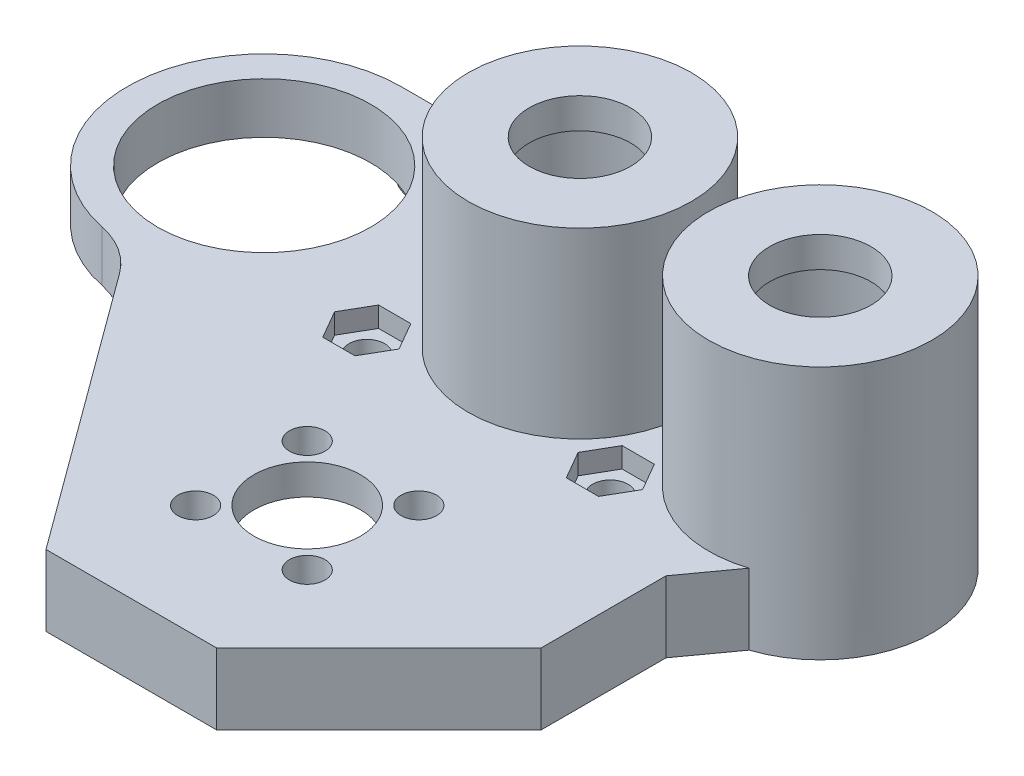
SolidWorks part; units mm, degrees
ref_plane "Front Plane" through (0, 0, 0) normal (0, 0, 1) x (1, 0, 0)
ref_plane "Top Plane" through (0, 0, 0) normal (0, 1, 0) x (1, 0, 0)
ref_plane "Right Plane" through (0, 0, 0) normal (1, 0, 0) x (0, 0, -1)
sketch "Sketch3" plane through (0, 0, 0) normal (0, 1, 0) x (1, 0, 0)
  line L1 (-31.113, 13.5) -> (23.69, 13.5)
  line L2 (-31.113, 13.5) -> (-31.113, -13.5)
  line L3 (-31.113, -13.5) -> (23.69, -13.5)
  line L4 (23.69, 13.5) -> (23.69, -13.5)
  line L5 (23.69, -13.5) -> (-31.113, -13.5)
  line L6 (23.69, -13.5) -> (23.69, -43.5)
  line L7 (23.69, -43.5) -> (-31.113, -43.5)
  line L8 (-31.113, -13.5) -> (-31.113, -43.5)
  circle A0 centre (-31.113, 0) radius 10.5
  circle A1 centre (-31.113, 0) radius 13.5
  circle A2 centre (0, -26.87) radius 5.25
  circle A3 centre (0, 0) radius 8
  circle A4 centre (23.69, 0) radius 8
  circle A5 centre (23.69, 0) radius 11
  dimension "D1" = 27
  dimension "D2" = 21
  dimension "D5" = 10.5
  dimension "D6" = 16
  dimension "D7" = 16
  dimension "D9" = 22
  dimension "D3" = 31.113
  dimension "D4" = 23.69
  dimension "D8" = 23.69
  dimension "D10" = 30
  dimension "D11" = 27
  dimension "D12" = 26.87
extrude "Boss-Extrude1" add sketch "Sketch3" along normal blind 7 contours L2 A1 A0 | A5 L4 L1 A1 L3 A3 | L2 A1 A0 | L4 A5 A4 | L3 L8 L7 L6 A2 | L4 A5 A4 region at (-21.7805, 0, -9.3325) region at (-3.7115, 0, -12.8891) region at (-31.4149, 0, -12) region at (-3.7115, 0, 14.1248) region at (31.2942, 0, -7.6042) region at (23.444, 0, -9.5)
sketch "Sketch4" plane through (0, 0, 0) normal (0, 1, 0) x (1, 0, 0)
  circle A0 centre (5.5, -21.37) radius 1.75
  circle A1 centre (0, -26.87) radius 5.25 construction
  circle A2 centre (5.5, -32.37) radius 1.75
  circle A3 centre (-5.5, -32.37) radius 1.75
  circle A4 centre (-5.5, -21.37) radius 1.75
  dimension "D3" = 3.5
  dimension "D4" = 3.5
  dimension "D7" = 3.5
  dimension "D9" = 3.5
  dimension "D1" = 5.5
  dimension "D2" = 5.5
  dimension "D5" = 5.5
  dimension "D6" = 5.5
  dimension "D8" = 11
  dimension "D10" = 11
  dimension "D11" = 11
  dimension "D12" = 11
extrude "Cut-Extrude3" cut sketch "Sketch4" along normal through all both and the other way through all
sketch "Sketch6" plane through (0, 7, 0) normal (0, 1, 0) x (1, 0, 0)
  circle A0 centre (23.69, 0) radius 8 construction
  circle A1 centre (0, 0) radius 8 construction
  circle A2 centre (23.69, 0) radius 8
  circle A3 centre (0, 0) radius 8
  circle A4 centre (23.69, 0) radius 11
  circle A5 centre (0, 0) radius 11
  dimension "D1" = 22
extrude "Boss-Extrude2" add sketch "Sketch6" along normal blind 15
sketch "Sketch7" plane through (0, 22, 0) normal (0, 1, 0) x (1, 0, 0)
  circle A0 centre (23.69, 0) radius 11 construction
  circle A1 centre (0, 0) radius 11 construction
  circle A2 centre (23.69, 0) radius 11
  circle A3 centre (0, 0) radius 11
  circle A4 centre (0, 0) radius 5
  circle A5 centre (23.69, 0) radius 5
  dimension "D1" = 10
  dimension "D2" = 10
extrude "Boss-Extrude3" add sketch "Sketch7" along normal blind 3
chamfer "Chamfer1" distance 2.5 angle 45 1 edges at (23.69, 3.5, -11)
sketch "Sketch8" plane through (0, 0, 0) normal (0, 1, 0) x (1, 0, 0)
  line L0 (-31.113, 0) -> (-31.113, 12.25)
  line L1 (-31.113, -13.5) -> (-51.113, -13.5)
  line L2 (-31.113, -13.5) -> (-31.113, 13.5)
  line L3 (-31.113, 13.5) -> (-51.113, 13.5)
  line L4 (-51.113, -13.5) -> (-51.113, 13.5)
  line L5 (-31.113, 12.25) -> (-13.613, 6.5)
  line L6 (-13.613, 6.5) -> (-13.613, -6.5)
  line L7 (-13.613, -6.5) -> (-31.113, -12.25)
  line L8 (-31.113, -12.25) -> (-31.113, 0)
  dimension "D1" = 20
  dimension "D2" = 12.25
  dimension "D3" = 12.25
  dimension "D4" = 27
  dimension "D5" = 17.5
  dimension "D6" = 6.5
  dimension "D7" = 6.5
extrude "Cut-Extrude4" cut sketch "Sketch8" along normal blind 2 contours L4 L1 L2 L0 L3 | L7 L6 L5 L0 L2 region at (-41.113, 0, 0) region at (-23.2574, 0, 0)
sketch "Sketch9" plane through (0, 0, 0) normal (0, 1, 0) x (1, 0, 0)
  circle A0 centre (12, 9) radius 1.75
  circle A1 centre (12, -9) radius 1.75
  circle A2 centre (-12, -9) radius 1.75
  circle A3 centre (-12, 9) radius 1.75
  dimension "D3" = 3.5
  dimension "D4" = 3.5
  dimension "D6" = 3.5
  dimension "D8" = 12
  dimension "D9" = 3.5
  dimension "D1" = 12
  dimension "D2" = 9
  dimension "D5" = 9
  dimension "D7" = 12
extrude "Cut-Extrude5" cut sketch "Sketch9" along normal through all both and the other way through all
sketch "Sketch10" plane through (0, 7, 0) normal (0, 1, 0) x (1, 0, 0)
  line L1 (-15.1754, -9) -> (-13.5877, -11.75)
  line L2 (-13.5877, -11.75) -> (-10.4123, -11.75)
  line L3 (-10.4123, -11.75) -> (-8.8246, -9)
  line L4 (-8.8246, -9) -> (-10.4123, -6.25)
  line L5 (-10.4123, -6.25) -> (-13.5877, -6.25)
  line L6 (-13.5877, -6.25) -> (-15.1754, -9)
  line L7 (-15.1754, 9) -> (-13.5877, 6.25)
  line L8 (-13.5877, 6.25) -> (-10.4123, 6.25)
  line L9 (-10.4123, 6.25) -> (-8.8246, 9)
  line L10 (-8.8246, 9) -> (-10.4123, 11.75)
  line L11 (-10.4123, 11.75) -> (-13.5877, 11.75)
  line L12 (-13.5877, 11.75) -> (-15.1754, 9)
  line L13 (15.1754, 9) -> (13.5877, 11.75)
  line L14 (13.5877, 11.75) -> (10.4123, 11.75)
  line L15 (10.4123, 11.75) -> (8.8246, 9)
  line L16 (8.8246, 9) -> (10.4123, 6.25)
  line L17 (10.4123, 6.25) -> (13.5877, 6.25)
  line L18 (13.5877, 6.25) -> (15.1754, 9)
  line L19 (15.1754, -9) -> (13.5877, -6.25)
  line L20 (13.5877, -6.25) -> (10.4123, -6.25)
  line L21 (10.4123, -6.25) -> (8.8246, -9)
  line L22 (8.8246, -9) -> (10.4123, -11.75)
  line L23 (10.4123, -11.75) -> (13.5877, -11.75)
  line L24 (13.5877, -11.75) -> (15.1754, -9)
  circle A0 centre (12, -9) radius 1.75 construction
  circle A1 centre (12, 9) radius 1.75 construction
  circle A2 centre (-12, 9) radius 1.75 construction
  circle A3 centre (-12, -9) radius 1.75 construction
  circle A4 centre (12, -9) radius 1.75
  circle A5 centre (12, 9) radius 1.75
  circle A6 centre (-12, 9) radius 1.75
  circle A7 centre (-12, -9) radius 1.75
  circle A8 centre (-12, -9) radius 2.75 construction
  circle A9 centre (-12, 9) radius 2.75 construction
  circle A10 centre (12, 9) radius 2.75 construction
  circle A11 centre (12, -9) radius 2.75 construction
  dimension "D1" = 5.5
  dimension "D2" = 5.5
  dimension "D3" = 5.5
  dimension "D4" = 5.5
extrude "Cut-Extrude6" cut sketch "Sketch10" against normal blind 2
chamfer "Chamfer2" distance 5 angle 45 1 edges at (23.69, 3.5, 11)
chamfer "Chamfer3" distance 30 distance2 22 1 edges at (-31.113, 3.5, 43.5) first distance on face at (-31.113, 3, 23.0833)
chamfer "Chamfer4" distance 16 angle 45 1 edges at (23.69, 3.5, 43.5)
fillet "Fillet1" radius 8 1 edges at (-31.113, 4.5, 13.5)
sketch "Sketch12" plane through (0, 7, 0) normal (0, 1, 0) x (1, 0, 0)
  line L1 (-19.4184, -1.5) -> (-9.2882, -1.5)
  line L2 (-19.4184, -1.5) -> (-19.4184, 1.5)
  line L3 (-19.4184, 1.5) -> (-9.2882, 1.5)
  line L4 (-9.2882, -1.5) -> (-9.2882, 1.5)
  line L5 (13.6189, -1.5) -> (8.9767, -1.5)
  line L6 (13.6189, -1.5) -> (13.6189, 1.5)
  line L7 (13.6189, 1.5) -> (8.9767, 1.5)
  line L8 (8.9767, -1.5) -> (8.9767, 1.5)
  arc A0 (26.5751, 10.6149) -> (27.1275, -10.4491) centre (23.69, 0) ccw construction
  circle A1 centre (0, 0) radius 11 construction
  circle A2 centre (-31.113, 0) radius 10.5 construction
  arc A3 (26.5751, 10.6149) -> (27.1275, -10.4491) centre (23.69, 0) ccw
  circle A4 centre (0, 0) radius 11
  circle A5 centre (-31.113, 0) radius 10.5
  circle A6 centre (-31.113, 0) radius 13.5
  circle M30 centre (-31.113, 0) radius 10.5
  arc M39 (27.1275, -10.4491) -> (26.5751, 10.6149) centre (23.69, 0) cw
  arc M42 (-31.113, 13.5) -> (-33.8666, -13.2162) centre (-31.113, 0) ccw
  circle M45 centre (0, 0) radius 11
  dimension "D1" = 3
  dimension "D2" = 1.5
extrude "Boss-Extrude4" [suppressed] add sketch "Sketch12" along normal blind 5 contours L7 L5 M39 M45 | A6 L1 L3 M45 | L3 A6 L1 L2 M42 M30 | L1 A6 L3 L2
sketch "Sketch13" plane through (0, 7, 0) normal (0, 1, 0) x (1, 0, 0)
  line L0 (23.69, -15.1987) -> (23.69, -27.5) construction
  line L1 (23.69, -15.1987) -> (23.69, -27.5)
  line L3 (23.69, -37.58) -> (20.69, -37.58)
  line L4 (23.69, -37.58) -> (23.69, 1.8154)
  line L5 (23.69, 1.8154) -> (20.69, 1.8154)
  line L6 (20.69, -37.58) -> (20.69, 1.8154)
  line L7 (-22, -2.4764) -> (-25, -2.4764)
  line L8 (-22, -2.4764) -> (-22, -39.8517)
  line L9 (-22, -39.8517) -> (-25, -39.8517)
  line L10 (-25, -2.4764) -> (-25, -39.8517)
  line L16 (-29.0471, -16.3171) -> (-9.113, -43.5)
  line L17 (26.5751, 10.6149) -> (23.69, 13.5)
  line L18 (-29.0471, -16.3171) -> (-9.113, -43.5)
  line L19 (-9.113, -43.5) -> (7.69, -43.5)
  line L21 (23.69, -27.5) -> (23.69, -15.1987)
  line L22 (7.69, -43.5) -> (23.69, -27.5)
  line L23 (26.5751, 10.6149) -> (23.69, 13.5)
  line L24 (23.69, 13.5) -> (-31.113, 13.5)
  line L25 (23.69, -15.1987) -> (27.1275, -10.4491)
  line L26 (-9.113, -43.5) -> (7.69, -43.5)
  line L27 (7.69, -43.5) -> (23.69, -27.5)
  line L28 (23.69, -27.5) -> (23.69, -15.1987)
  line L29 (23.69, -15.1987) -> (27.1275, -10.4491)
  line L30 (23.69, 13.5) -> (-31.113, 13.5)
  arc A3 (-31.113, 13.5) -> (-33.8666, -13.2162) centre (-31.113, 0) ccw
  arc A4 (-31.113, 13.5) -> (-33.8666, -13.2162) centre (-31.113, 0) ccw
  arc A5 (-29.0471, -16.3171) -> (-33.8666, -13.2162) centre (-35.4984, -21.048) ccw
  arc A6 (26.5751, 10.6149) -> (27.1275, -10.4491) centre (23.69, 0) ccw
  arc A7 (-29.0471, -16.3171) -> (-33.8666, -13.2162) centre (-35.4984, -21.048) ccw
  arc A10 (26.5751, 10.6149) -> (27.1275, -10.4491) centre (23.69, 0) ccw
  arc M39 (-31.113, 13.5) -> (-33.8666, -13.2162) centre (-31.113, 0) ccw
  line M41 (-29.0471, -16.3171) -> (-9.113, -43.5)
  line M43 (7.69, -43.5) -> (23.69, -27.5)
  line M44 (23.69, -27.5) -> (23.69, -15.1987)
  arc M46 (27.1275, -10.4491) -> (26.5751, 10.6149) centre (23.69, 0) cw
  dimension "D2" = 3
  dimension "D3" = 3
  dimension "D5" = 0
  dimension "D1" = 0
extrude "Boss-Extrude5" [suppressed] add sketch "Sketch13" along normal blind 5 contours L6 L4 M43 M44 M46 | L10 L8 M39 M41
sketch "Sketch14" plane through (0, 0, 0) normal (0, -1, 0) x (1, 0, 0)
  line L12 (23.69, 15.1987) -> (23.69, 27.5)
  line L13 (23.69, 27.5) -> (7.69, 43.5)
  line L14 (7.69, 43.5) -> (-9.113, 43.5)
  line L16 (-31.113, 13.5) -> (-31.113, 12.25)
  line L17 (-31.113, 12.25) -> (-13.613, 6.5)
  line L18 (-13.613, 6.5) -> (-13.613, -6.5)
  line L19 (-13.613, -6.5) -> (-31.113, -12.25)
  line L20 (-31.113, -12.25) -> (-31.113, -13.5)
  line L21 (-31.113, -13.5) -> (23.69, -13.5)
  line L22 (23.69, -13.5) -> (26.5751, -10.6149)
  line L23 (23.69, 27.5) -> (7.69, 43.5)
  line L24 (23.69, 15.1987) -> (23.69, 27.5)
  line L26 (7.69, 43.5) -> (-9.113, 43.5)
  line L28 (-31.113, 13.5) -> (-31.113, 12.25)
  line L29 (-31.113, 12.25) -> (-13.613, 6.5)
  line L30 (-13.613, 6.5) -> (-13.613, -6.5)
  line L31 (-13.613, -6.5) -> (-31.113, -12.25)
  line L32 (-31.113, -12.25) -> (-31.113, -13.5)
  line L33 (-31.113, -13.5) -> (23.69, -13.5)
  line L34 (23.69, -13.5) -> (26.5751, -10.6149)
  line L36 (-9.113, 43.5) -> (-31.113, 13.5)
  line L37 (-9.113, 43.5) -> (-31.113, 13.5)
  line L38 (27.1275, 10.4491) -> (23.69, 15.1987)
  line L39 (27.1275, 10.4491) -> (23.69, 15.1987)
  circle A0 centre (0, 26.87) radius 5.25 construction
  arc A1 (26.5751, -10.6149) -> (27.1275, 10.4491) centre (23.69, 0) ccw
  arc A2 (26.5751, -10.6149) -> (27.1275, 10.4491) centre (23.69, 0) ccw
  circle A3 centre (0, 26.87) radius 5.25
  circle A4 centre (0, 26.87) radius 11.5
  circle M19 centre (0, 26.87) radius 5.25
  circle M22 centre (5.5, 21.37) radius 1.75
  circle M23 centre (5.5, 32.37) radius 1.75
  circle M24 centre (-5.5, 32.37) radius 1.75
  circle M25 centre (-5.5, 21.37) radius 1.75
  dimension "D2" = 23
  dimension "D1" = 0
extrude "Cut-Extrude8" cut sketch "Sketch14" against normal blind 4 contours A4 M19 M23 M25 M24 M22 region at (-11.1747, 0, 26.87)
fillet "Fillet2" radius 3 2 edges at (-31.113, 1, -12.25) (-31.113, 1, 12.25)
